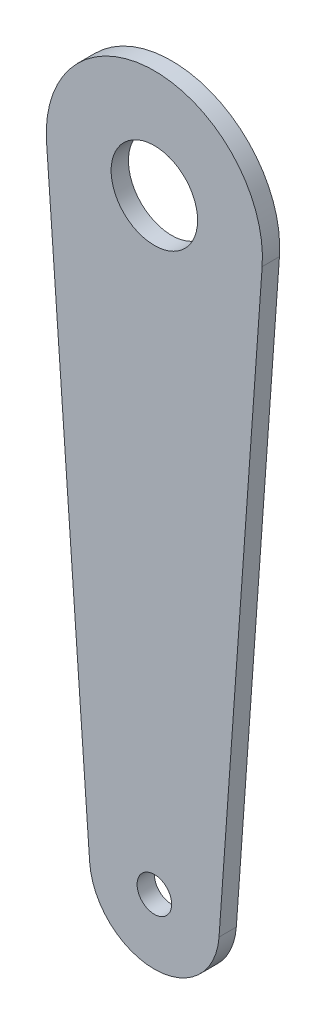
SolidWorks part; units mm, degrees
ref_plane "Alzado" through (0, 0, 0) normal (0, 0, 1) x (1, 0, 0)
ref_plane "Planta" through (0, 0, 0) normal (0, 1, 0) x (1, 0, 0)
ref_plane "Vista lateral" through (0, 0, 0) normal (1, 0, 0) x (0, 0, -1)
sketch "Croquis1" plane through (0, 0, 0) normal (0, 0, 1) x (1, 0, 0)
  line L0 (0, 128.425) -> (0, -11.575) construction
  line L1 (-14.9617, -12.6464) -> (-25.064, 128.425)
  line L2 (14.9617, -12.6464) -> (24.9361, 126.6393)
  arc A0 (-14.9617, -12.6464) -> (14.9617, -12.6464) centre (0, -11.575) ccw
  arc A1 (24.9361, 126.6393) -> (-24.9361, 126.6393) centre (0, 128.425) ccw
  circle A2 centre (0, 128.425) radius 10
  circle A3 centre (0, -11.575) radius 4
  dimension "D1" = 30
  dimension "D2" = 50
  dimension "D4" = 20
  dimension "D5" = 8
  dimension "D3" = 140
extrude "Saliente-Extruir1" add sketch "Croquis1" along normal blind 4 contours L2 A1 L1 A0 A2 A3 region at (0, 68.5114, 0)
